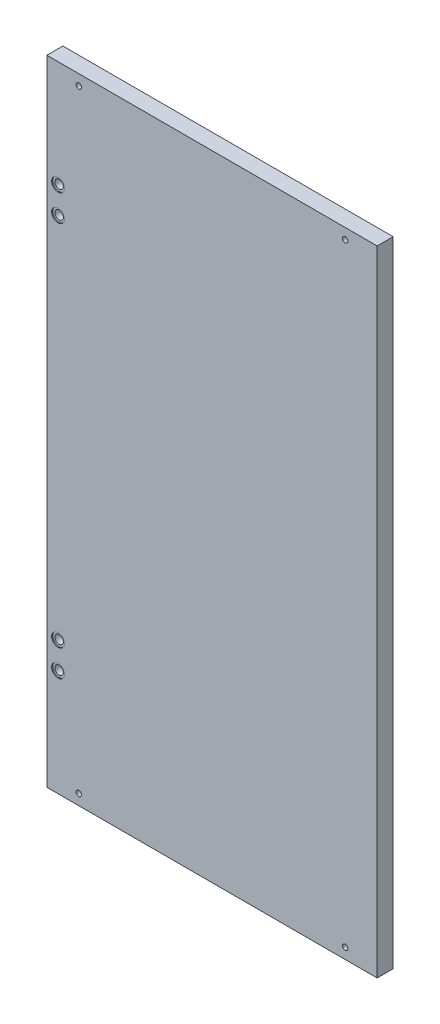
SolidWorks part; units mm, degrees
material "西洋杉"
ref_plane "正面" through (0, 0, 0) normal (0, 0, 1) x (1, 0, 0)
ref_plane "平面" through (0, 0, 0) normal (0, 1, 0) x (1, 0, 0)
ref_plane "右側面" through (0, 0, 0) normal (1, 0, 0) x (0, 0, -1)
sketch "ｽｹｯﾁ1" plane through (0, 0, 0) normal (0, 0, 1) x (1, 0, 0)
  line L1 (-155, 297.5) -> (155, 297.5)
  line L2 (-155, 297.5) -> (-155, -297.5)
  line L3 (-155, -297.5) -> (155, -297.5)
  line L4 (155, 297.5) -> (155, -297.5)
  line L5 (-155, 297.5) -> (155, -297.5) construction
  line L6 (-155, -297.5) -> (155, 297.5) construction
  point P0 (0, 0)
  dimension "D1" = 595
  dimension "D2" = 310
extrude "ﾎﾞｽ - 押し出し1" add sketch "ｽｹｯﾁ1" along normal blind 15
sketch "ｽｹｯﾁ2" plane through (0, 0, 15) normal (0, 0, 1) x (1, 0, 0)
  line L0 (-144.5, 297.5) -> (-144.5, -297.5) construction
  line L1 (155, 297.5) -> (-155, 297.5) construction
  line L2 (-155, -297.5) -> (155, -297.5) construction
  line L3 (-155, 297.5) -> (-155, -297.5) construction
  line L4 (-155, 287.5) -> (155, 287.5) construction
  line L5 (155, -297.5) -> (155, 297.5) construction
  circle A0 centre (-144.5, 197.5) radius 4
  circle A6 centre (-125, 287.5) radius 2.5
  circle A7 centre (-144.5, 172.5) radius 4
  dimension "D2" = 8
  dimension "D4" = 5
  dimension "D8" = 8
  dimension "D1" = 10.5
  dimension "D3" = 100
  dimension "D5" = 10
  dimension "D6" = 310
  dimension "D10" = 595
  dimension "D7" = 30
  dimension "D9" = 25
extrude "ｶｯﾄ - 押し出し2" cut sketch "ｽｹｯﾁ2" against normal through all contours A0 | A7
extrude "ｶｯﾄ - 押し出し3" cut sketch "ｽｹｯﾁ2<5>" against normal through all contours A6
sketch "ｽｹｯﾁ2<5>" plane through (0, 0, 15) normal (0, 0, 1) x (1, 0, 0) same geometry as "ｽｹｯﾁ2"
mirror "ﾐﾗｰ1" about plane through (0, 0, 0) normal (0, 1, 0) of "ｶｯﾄ - 押し出し3"
mirror "ﾐﾗｰ2" about plane through (0, 0, 0) normal (0, 1, 0) of "ｶｯﾄ - 押し出し2"
mirror "ﾐﾗｰ3" about plane through (0, 0, 0) normal (1, 0, 0) of "ﾐﾗｰ1"
sketch "ｽｹｯﾁ3" plane through (0, 0, 15) normal (0, 0, 1) x (1, 0, 0)
  circle A0 centre (-144.5, 197.5) radius 6
  circle A1 centre (-144.5, 172.5) radius 6
  dimension "D1" = 12
  dimension "D2" = 12
extrude "ｶｯﾄ - 押し出し4" cut sketch "ｽｹｯﾁ3" against normal blind 1
mirror "ﾐﾗｰ4" about plane through (0, 0, 0) normal (0, 1, 0) of "ｶｯﾄ - 押し出し4"
equation "\"D8@ｽｹｯﾁ2\"=\"D2@ｽｹｯﾁ2\""
